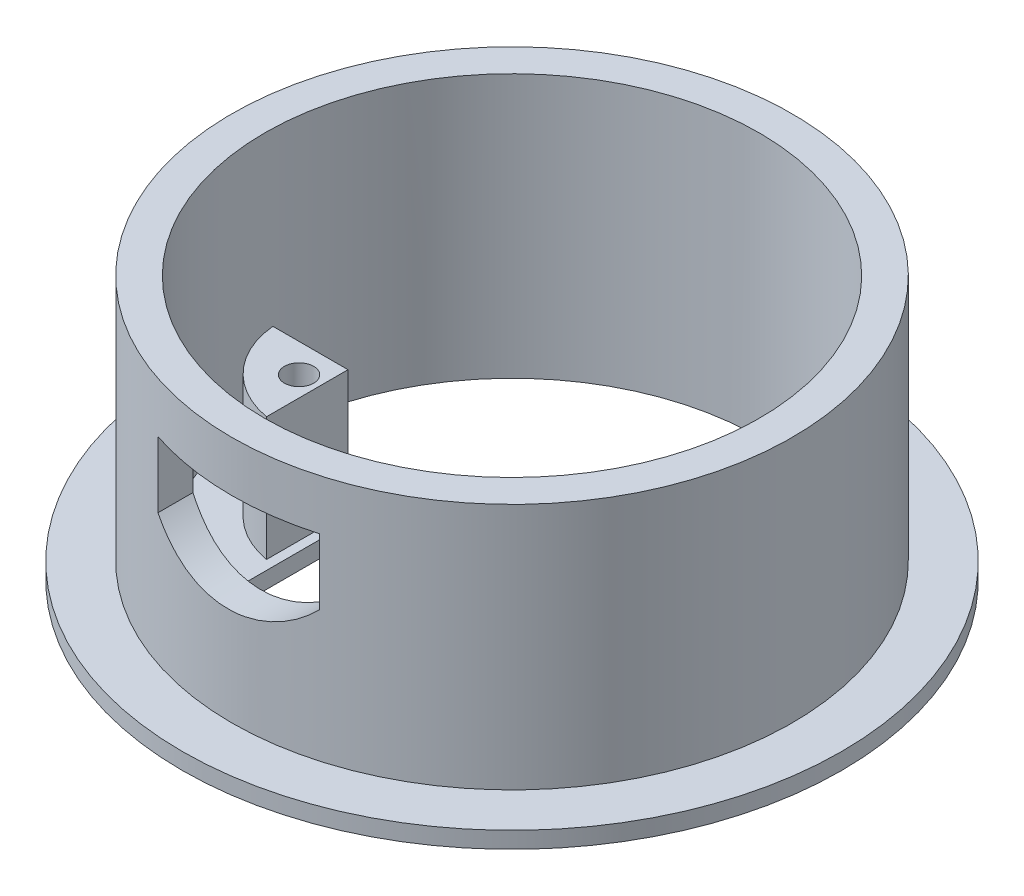
SolidWorks part; units mm, degrees
ref_plane "Front Plane" through (0, 0, 0) normal (0, 0, 1) x (1, 0, 0)
ref_plane "Top Plane" through (0, 0, 0) normal (0, 1, 0) x (1, 0, 0)
ref_plane "Right Plane" through (0, 0, 0) normal (1, 0, 0) x (0, 0, -1)
sketch "Sketch1" plane through (0, 0, 0) normal (0, 1, 0) x (1, 0, 0)
  circle A0 centre (0, 0) radius 40
  circle A1 centre (0, 0) radius 30
  dimension "D1" = 80
  dimension "D2" = 60
extrude "Boss-Extrude1" add sketch "Sketch1" along normal blind 2
sketch "Sketch2" plane through (0, 2, 0) normal (0, 1, 0) x (1, 0, 0)
  circle A0 centre (0, 0) radius 30 construction
  circle A1 centre (0, 0) radius 30
  circle A2 centre (0, 0) radius 34
  dimension "D1" = 4
extrude "Boss-Extrude2" add sketch "Sketch2" along normal blind 30
ref_plane "Plane1" through (0, 12, 0) normal (0, 1, 0) x (1, 0, 0)
sketch "Sketch9" plane through (0, 0, 0) normal (0, 1, 0) x (1, 0, 0)
  line L0 (-29.8657, -2.8351) -> (29.8657, -2.8351)
  line L1 (0, 30) -> (0, -48.3805) construction
  line L2 (-30, 0) -> (59.405, 0) construction
  circle A0 centre (0, 0) radius 30 construction
  arc A1 (29.8657, -2.8351) -> (0, -30) centre (0, 0) cw
  arc A2 (-29.8657, -2.8351) -> (0, -30) centre (0, 0) ccw
extrude "Boss-Extrude3" add sketch "Sketch9" along normal blind 2
sketch "Sketch11" plane through (0, 2, 0) normal (0, 1, 0) x (1, 0, 0)
  line L0 (-24.1735, -4.8351) -> (-15.0625, -4.8351)
  line L1 (-15.0625, -4.8351) -> (-15.0625, -14.7177)
  line L2 (0, 30) -> (0, 39.1404) construction
  line L3 (24.1735, -4.8351) -> (15.0625, -4.8351)
  line L4 (15.0625, -4.8351) -> (15.0625, -14.7177)
  line L5 (-29.8657, -2.8351) -> (29.8657, -2.8351) construction
  arc A0 (-24.1735, -4.8351) -> (-15.0625, -14.7177) centre (-13.1735, -3.8351) ccw
  arc A1 (24.1735, -4.8351) -> (15.0625, -14.7177) centre (13.1735, -3.8351) cw
  dimension "D1" = 2
ref_plane "Plane2" through (0, 0, 35) normal (0, 0, 1) x (1, 0, 0)
sketch "Sketch10" plane through (0, 0, 35) normal (0, 0, 1) x (1, 0, 0)
  line L0 (-10.6683, 25.8895) -> (9.3317, 25.8895)
  line L1 (9.3317, 25.8895) -> (9.3317, 17.8895)
  line L2 (-10.6683, 25.8895) -> (-10.6683, 17.8895)
  arc A0 (9.3317, 17.8895) -> (-10.6683, 17.8895) centre (-0.6683, 27.8895) cw
extrude "Cut-Extrude1" cut sketch "Sketch10" against normal blind 7
extrude "Boss-Extrude4" add sketch "Sketch11" along normal blind 15
sketch "Sketch12" plane through (0, 17, 0) normal (0, 1, 0) x (1, 0, 0)
  line L0 (0, 0) -> (0, 7.1822) construction
  line L1 (0, 30) -> (0, -48.3805) construction
  line L2 (-15.0625, -4.8351) -> (-24.1735, -4.8351) construction
  circle A0 centre (-17.5, -8.3351) radius 1.775
  circle A1 centre (17.5, -8.3351) radius 1.775
  dimension "D1" = 35
  dimension "D2" = 3.5
extrude "Cut-Extrude2" cut sketch "Sketch12" against normal blind 9
sketch "Sketch13" plane through (0, 2, 0) normal (0, 1, 0) x (1, 0, 0)
  line L0 (-13.9184, -20.8807) -> (-13.9184, 1.1193)
  line L1 (-13.9184, 1.1193) -> (14.0816, 1.1193)
  line L2 (14.0816, 1.1193) -> (14.0816, -20.8807)
  arc A0 (14.0816, -20.8807) -> (-13.9184, -20.8807) centre (0.0816, -8.9643) cw
  dimension "D1" = 28
extrude "Cut-Extrude3" cut sketch "Sketch13" against normal blind 10
